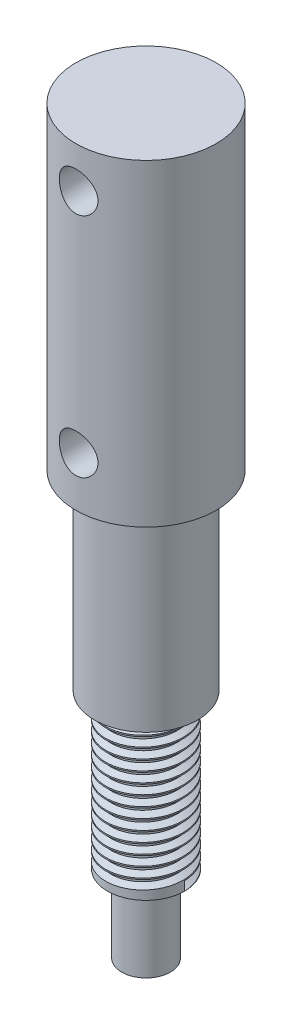
SolidWorks part; units mm, degrees
material "AISI 316 Annealed Stainless Steel Bar (SS)"
ref_plane "Front Plane" through (0, 0, 0) normal (0, 0, 1) x (1, 0, 0)
ref_plane "Top Plane" through (0, 0, 0) normal (0, 1, 0) x (1, 0, 0)
ref_plane "Right Plane" through (0, 0, 0) normal (1, 0, 0) x (0, 0, -1)
sketch "Sketch2" plane through (0, 0, 0) normal (0, 0, 1) x (1, 0, 0)
  line L0 (0, 0) -> (0, 508.8276) construction
  line L1 (0, 0) -> (6, 0)
  line L2 (0, 0) -> (0, 19.05)
  line L3 (0, 19.05) -> (6, 19.05)
  line L4 (6, 0) -> (6, 19.05)
  line L5 (0, 19.05) -> (9.525, 19.05)
  line L6 (0, 19.05) -> (0, 57.15)
  line L7 (0, 57.15) -> (9.525, 57.15)
  line L8 (9.525, 19.05) -> (9.525, 57.15)
  line L9 (0, 57.15) -> (12.721, 57.15)
  line L10 (0, 57.15) -> (0, 104.14)
  line L11 (0, 104.14) -> (12.721, 104.14)
  line L12 (12.721, 57.15) -> (12.721, 104.14)
  line L13 (0, 104.14) -> (17.272, 104.14)
  line L14 (0, 104.14) -> (0, 182.372)
  line L15 (0, 182.372) -> (17.272, 182.372)
  line L16 (17.272, 104.14) -> (17.272, 182.372)
  dimension "D1" = 78.232
  dimension "D2" = 17.272
  dimension "D4" = 46.99
  dimension "D3" = 12.721
  dimension "D5" = 38.1
  dimension "D6" = 9.525
  dimension "D7" = 19.05
  dimension "D8" = 6
revolve "Revolve1" add sketch "Sketch2" angle 360 about L0 region at (3, 9.525, 0) region at (4.7625, 38.1, 0) region at (6.3605, 80.645, 0) region at (8.636, 143.256, 0)
thread "Thread2" pitch 2.54 method cut profile "Thread Profile3" start angle 0, offset 0, length 0, pitch 2.54, diameter 19.05
ref_plane "Plane3" through (9.525, 19.05, 0) normal (0, 0, 1) x (1, 0, 0)
sketch "Thread Profile3" plane through (9.525, 19.05, 0) normal (0, 0, 1) x (1, 0, 0)
  line L0 (0, 0) -> (0, 2.54) construction
  line L11 (0, 0) -> (0, 2.2225)
  line L12 (0, 2.2225) -> (-1.3748, 1.4287)
  line L13 (-1.3748, 1.4287) -> (-1.3748, 0.7937)
  line L15 (-1.3748, 0.7937) -> (0, 0)
  line L17 (-1.3748, 1.1112) -> (0, 1.1112) construction
  point P2 (0, 0)
  dimension "Pitch" = 2.54
  dimension "Profile_Angle" = 60
  dimension "Profile_Land" = 0.635
  dimension "Profile_Height" = 1.3748
sketch "Sketch3" plane through (0, 0, 0) normal (0, 0, 1) x (1, 0, 0)
  line L0 (0, 0) -> (0, 197.3408) construction
  line L1 (17.272, 182.372) -> (-17.272, 182.372) construction
  circle A0 centre (0, 172.212) radius 4.7625
  circle A1 centre (0, 116.332) radius 4.7625
  dimension "D1" = 9.525
  dimension "D2" = 10.16
  dimension "D3" = 66.04
extrude "Cut-Extrude1" cut sketch "Sketch3" against normal through all both and the other way through all
equation "\"hole diamiter\"= 1.36in"
equation "\"wheel depth\"= 2.88"
equation "\"press_tolerance\"= 0.00165"
equation "\"wheel_connection\"= \"hole diamiter\"'https://at-machining.com/tolerance-press-fit/"
equation "\"D1@Sketch2\"=\"wheel depth\"+0.2"
equation "\"D2@Sketch2\"=\"wheel_connection\"/2"
equation "\"fitting depth\"= 1.85"
equation "\"D4@Sketch2\"=\"fitting depth\""
equation "\"bearing_id\"= 1"
equation "\"bearing_connection\"= \"bearing_id\" + \"press_tolerance\"'https://at-machining.com/tolerance-press-fit/"
equation "\"D3@Sketch2\"=\"bearing_connection\"/2"
equation "\"thread length\"= 1.5"
equation "\"major_diamiter\"= 0.75 'https://www.machiningdoctor.com/threadinfo/?tid=81"
equation "\"D5@Sketch2\"=\"thread length\""
equation "\"D6@Sketch2\"=\"major_diamiter\"/2"
equation "\"coupling diamiter\"= 12mm"
equation "\"coupling lenght\"= 1.5 / 2"
equation "\"D7@Sketch2\"=\"coupling lenght\""
equation "\"D8@Sketch2\"=\"coupling diamiter\"/2"
